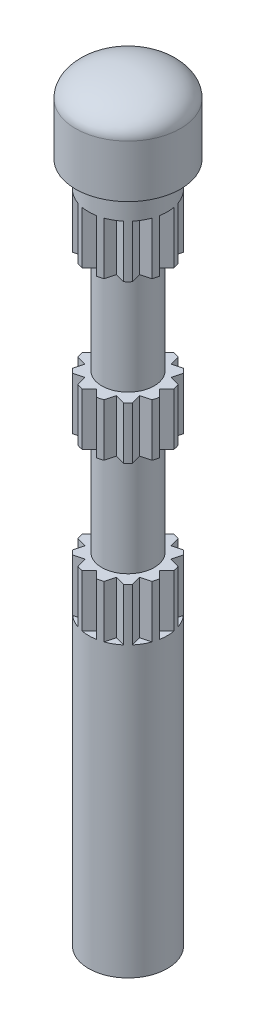
SolidWorks part; units mm, degrees
ref_plane "前视基准面" through (0, 0, 0) normal (0, 0, 1) x (1, 0, 0)
ref_plane "上视基准面" through (0, 0, 0) normal (0, 1, 0) x (1, 0, 0)
ref_plane "右视基准面" through (0, 0, 0) normal (1, 0, 0) x (0, 0, -1)
sketch "草图1" plane through (0, 0, 0) normal (0, 0, 1) x (1, 0, 0)
  line L0 (0, 0) -> (2, 0)
  line L1 (2, 0) -> (2, 14)
  line L2 (0, 0) -> (0, 14)
  line L3 (1, 20.1107) -> (1, -7.8022) construction
  ellipse E0 centre (1, 14) end of major axis (2, 14) minor radius 0.5
  dimension "D1" = 0.5
  dimension "D2" = 2
  dimension "D3" = 14
  dimension "D4" = 0.5
revolve "旋转1" add sketch "草图1" angle 360 about L3 region at (1.5022, 6.8041, 0) region at (1.4244, 14, 0)
sketch "草图2" plane through (0, 0, 0) normal (0, -1, 0) x (1, 0, 0)
  circle A0 centre (1, 0) radius 1.2882
  circle A1 centre (1, 0) radius 0.75
  dimension "D1" = 1.5
extrude "切除-拉伸1" cut sketch "草图2" against normal blind 13
sketch "草图3" plane through (0, 0, 0) normal (0, -1, 0) x (-1, 0, 0)
  circle A0 centre (-1, 0) radius 0.4
  dimension "D1" = 0.8
extrude "切除-拉伸2" cut sketch "草图3" against normal blind 5
ref_plane "基准面1" through (0, 5.5, 0) normal (0, -1, 0) x (-1, 0, 0)
sketch "草图4" plane through (0, 5.5, 0) normal (0, -1, 0) x (-1, 0, 0)
  circle A0 centre (-1, 0) radius 0.75
curve "螺旋线/涡状线1" [suppressed] pitch 9 height 9 turns 1
sketch "草图5" [suppressed] plane through (0, 0, 0) normal (0, 0, 1) x (1, 0, 0)
  line L0 (1.75, 0) -> (1.75, 15) construction
  line L1 (1.775, 4.9567) -> (1.7, 5)
  line L2 (1.7, 5) -> (1.775, 5.0433)
  line L3 (1.775, 5.0433) -> (1.775, 4.9567)
  circle A0 centre (1.75, 5) radius 0.025 construction
  spline S0 degree 3 poles (1.75, 5) (1.75, 5.1872) (1.7109, 5.5626) (1.5441, 6.125) (1.2945, 6.6875) (1, 7.25) (0.7055, 7.8125) (0.4559, 8.375) (0.2891, 8.9375) (0.2305, 9.5) (0.2891, 10.0625) (0.4559, 10.625) (0.7055, 11.1875) (1, 11.75) (1.2945, 12.3125) (1.5441, 12.875) (1.7109, 13.4374) (1.75, 13.8128) (1.75, 14) knots 0 0 0 0 0.0625 0.125 0.1875 0.25 0.3125 0.375 0.4375 0.5 0.5625 0.625 0.6875 0.75 0.8125 0.875 0.9375 1 1 1 1 construction
  dimension "D1" = 0.05
sweep "切除-扫描1" [suppressed] cut profiles "草图5" path "螺旋线/涡状线1"
pattern_circular "阵列(圆周)10" [suppressed] count 30 over 360 reverse direction yes of bodies 109
sketch "草图6" plane through (0, 5.5, 0) normal (0, -1, 0) x (-1, 0, 0)
  circle A0 centre (-1, 0) radius 0.75
curve "螺旋线/涡状线2" [suppressed] pitch 9 height 9 turns 1
sketch "草图7" [suppressed] plane through (0, 0, 0) normal (0, 0, 1) x (1, 0, 0)
  line L0 (1.75, 5.0289) -> (1.75, 4.9711) construction
  line L1 (1.7, 5) -> (1.775, 4.9567)
  line L2 (1.775, 4.9567) -> (1.775, 5.0433)
  line L3 (1.775, 5.0433) -> (1.7, 5)
  circle A0 centre (1.75, 5) radius 0.025 construction
  dimension "D1" = 0.05
sweep "切除-扫描2" [suppressed] cut profiles "草图7" path "螺旋线/涡状线2"
pattern_circular "阵列(圆周)12" [suppressed] count 20 over 360 of bodies 112
sketch "草图8" plane through (0, 0, 0) normal (0, 0, 1) x (1, 0, 0)
  line L0 (1, 0) -> (1, 21.5854) construction
  line L1 (0.25, 0) -> (1.75, 0) construction
  line L2 (0.25, 13) -> (1.75, 13) construction
  line L3 (1.9435, 11.5) -> (1.5, 11.5)
  line L4 (1.9435, 11.5) -> (1.9435, 9.5)
  line L5 (1.9435, 9.5) -> (1.5, 9.5)
  line L6 (1.5, 11.5) -> (1.5, 9.5)
  line L7 (1.9435, 8.5) -> (1.5, 8.5)
  line L8 (1.9435, 8.5) -> (1.9435, 6.5)
  line L9 (1.9435, 6.5) -> (1.5, 6.5)
  line L10 (1.5, 8.5) -> (1.5, 6.5)
  dimension "D1" = 2
  dimension "D2" = 2
  dimension "D3" = 0.5
  dimension "D4" = 0.5
  dimension "D5" = 1
  dimension "D6" = 6.5
  dimension "D7" = 6.5
revolve "切除-旋转1" cut sketch "草图8" angle 360 about L0
sketch "草图9" plane through (0, 5.5, 0) normal (0, -1, 0) x (-1, 0, 0)
  line L0 (-1, 0.6) -> (-1, 0.75)
  line L1 (-1, 0.6) -> (-0.8627, 0.7373)
  line L2 (-1, 0.6) -> (-1.1373, 0.7373)
  circle A0 centre (-1, 0) radius 0.75
  circle A1 centre (-1, 0) radius 0.6
  dimension "D1" = 1.5
  dimension "D2" = 1.2
  dimension "D3" = 45
  dimension "D4" = 45
extrude "切除-拉伸3" cut sketch "草图9" against normal blind 7 contours L0 A0 L2 | L1 A0 L0 region at (1.0464, 5.5, -0.6971) region at (0.9536, 5.5, -0.6971)
pattern_circular "阵列(圆周)13" count 12 over 360 about axis through (1, 13, 0) along (0, -1, 0) of "切除-拉伸3" reverse direction yes
